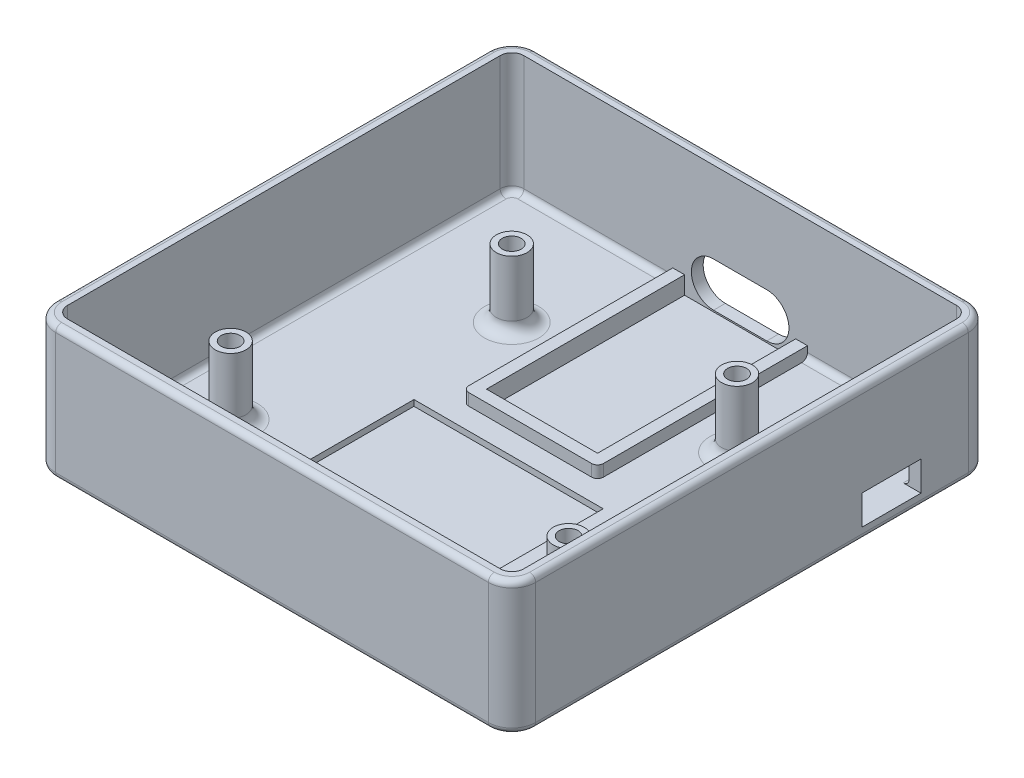
SolidWorks part; units mm, degrees
ref_plane "Front Plane" through (0, 0, 0) normal (0, 0, 1) x (1, 0, 0)
ref_plane "Top Plane" through (0, 0, 0) normal (0, 1, 0) x (1, 0, 0)
ref_plane "Right Plane" through (0, 0, 0) normal (1, 0, 0) x (0, 0, -1)
sketch "Sketch1" plane through (0, 0, 0) normal (0, 1, 0) x (1, 0, 0)
  line L1 (-38.575, -38.575) -> (38.575, -38.575)
  line L2 (-38.575, -38.575) -> (-38.575, 38.575)
  line L3 (-38.575, 38.575) -> (38.575, 38.575)
  line L4 (38.575, -38.575) -> (38.575, 38.575)
  line L5 (-38.575, -38.575) -> (38.575, 38.575) construction
  line L6 (-38.575, 38.575) -> (38.575, -38.575) construction
  point P0 (0, 0)
  dimension "D1" = 77.15
extrude "Boss-Extrude1" add sketch "Sketch1" along normal blind 2
sketch "Sketch2" plane through (0, 0, 0) normal (0, 1, 0) x (1, 0, 0)
  line L20 (38.575, -38.575) -> (38.575, 38.575) construction
  line L21 (38.575, 38.575) -> (-38.575, 38.575) construction
  line L22 (-38.575, 38.575) -> (-38.575, -38.575) construction
  line L23 (-38.575, -38.575) -> (38.575, -38.575) construction
  line L24 (40.575, -40.575) -> (40.575, 40.575)
  line L25 (40.575, 40.575) -> (-40.575, 40.575)
  line L26 (-40.575, 40.575) -> (-40.575, -40.575)
  line L27 (-40.575, -40.575) -> (40.575, -40.575)
  line L28 (40.575, -40.575) -> (40.575, 40.575)
  line L29 (40.575, 40.575) -> (-40.575, 40.575)
  line L30 (-40.575, 40.575) -> (-40.575, -40.575)
  line L31 (-40.575, -40.575) -> (40.575, -40.575)
  line L32 (38.575, -38.575) -> (38.575, 38.575)
  line L33 (38.575, 38.575) -> (-38.575, 38.575)
  line L34 (-38.575, 38.575) -> (-38.575, -38.575)
  line L35 (-38.575, -38.575) -> (38.575, -38.575)
  dimension "D1" = 2
extrude "Boss-Extrude2" add sketch "Sketch2" along normal blind 22.5
sketch "Sketch3" plane through (0, 2, 0) normal (0, 1, 0) x (1, 0, 0)
  line L0 (28.58, -19) -> (-28.58, -19) construction
  line L2 (19.05, 19) -> (-19.05, 19) construction
  circle A2 centre (-28.58, -19) radius 1.6
  circle A3 centre (28.58, -19) radius 1.6
  circle A4 centre (19.05, 19) radius 1.6
  circle A5 centre (-19.05, 19) radius 1.6
  circle A6 centre (-28.58, -19) radius 2.6
  circle A7 centre (-19.05, 19) radius 2.6
  circle A8 centre (28.58, -19) radius 2.6
  circle A9 centre (19.05, 19) radius 2.6
  point P0 (0, 0)
  point P2 (0, 19)
  point P17 (0, -19)
  dimension "D3" = 1
  dimension "D4" = 19
  dimension "D1" = 3.2
  dimension "D2" = 38.1
  dimension "D5" = 57.16
  dimension "D6" = 19
extrude "Boss-Extrude4" add sketch "Sketch3" along normal offset from surface (11.5 mm away) 9 up to face at (0, 22.5, 0)
sketch "Sketch4" plane through (0, 0, 0) normal (1, 0, 0) x (0, 0, -1)
  line L0 (0, 0) -> (0, 22.5) construction
  line L1 (-40.575, 22.5) -> (40.575, 22.5) construction
sketch "Sketch11" plane through (0, 2, 0) normal (0, 1, 0) x (1, 0, 0)
  line L0 (-15, -31.575) -> (-15, -1.575)
  line L6 (-16, -32.575) -> (16, -32.575)
  line L7 (-16, -32.575) -> (-16, -0.575)
  line L8 (-16, -0.575) -> (16, -0.575)
  line L9 (16, -32.575) -> (16, -0.575)
  line L10 (-16, -32.575) -> (16, -0.575) construction
  line L11 (-16, -0.575) -> (16, -32.575) construction
  line L12 (38.575, 38.575) -> (-38.575, 38.575) construction
  line L13 (-8.89, 38.575) -> (8.89, 38.575) construction
  line L14 (-8.89, 38.575) -> (-8.89, 5.575) construction
  line L15 (-8.89, 5.575) -> (8.89, 5.575) construction
  line L16 (8.89, 38.575) -> (8.89, 5.575) construction
  line L17 (-8.89, 38.575) -> (8.89, 5.575) construction
  line L18 (-8.89, 5.575) -> (8.89, 38.575) construction
  line L27 (-15, -1.575) -> (15, -1.575)
  line L28 (15, -31.575) -> (15, -1.575)
  line L29 (-15, -31.575) -> (15, -31.575)
  line L30 (0, -12.1) -> (0, 12.1) construction
  line L31 (4, 38.575) -> (5.5, 38.575)
  line L32 (4, 38.575) -> (4, 10.575)
  line L33 (4, 10.575) -> (5.5, 10.575)
  line L34 (5.5, 38.575) -> (5.5, 10.575)
  line L35 (-4, 10.575) -> (-5.5, 10.575)
  line L36 (-5.5, 38.575) -> (-5.5, 10.575)
  line L37 (-4, 38.575) -> (-5.5, 38.575)
  line L38 (-4, 38.575) -> (-4, 10.575)
  line L39 (-38.575, -38.575) -> (38.575, -38.575) construction
  point P1 (0, 22.075)
  point P6 (0, -16.575)
  dimension "D1" = 33
  dimension "D2" = 17.78
  dimension "D3" = 1
  dimension "D4" = 30
  dimension "D5" = 6
  dimension "D6" = 30
  dimension "D7" = 4
  dimension "D8" = 1.5
  dimension "D9" = 5
extrude "Boss-Extrude7" [suppressed] add sketch "Sketch11" along normal blind 1 contours L35 L36 L37 L38 | L32 L31 L34 L33
sketch "Sketch17" plane through (0, 2, 0) normal (0, 1, 0) x (1, 0, 0)
  line L16 (9.39, 11.075) -> (11.39, 11.075)
  line L17 (11.39, 11.075) -> (11.39, 3.075)
  line L18 (11.39, 3.075) -> (-11.39, 3.075)
  line L19 (-9.39, 5.075) -> (-9.39, 38.575)
  line L20 (9.39, 5.075) -> (-9.39, 5.075)
  line L21 (9.39, 38.575) -> (9.39, 5.075)
  line L22 (-9.39, 5.075) -> (-9.39, 11.075)
  line L23 (9.39, 5.075) -> (-9.39, 5.075)
  line L24 (9.39, 11.075) -> (9.39, 5.075)
  line L25 (-11.39, 3.075) -> (-11.39, 11.075)
  line L26 (-11.39, 11.075) -> (-9.39, 11.075)
  dimension "D1" = 0.5
  dimension "D2" = 2
  dimension "D3" = 2
  dimension "D4" = 8
extrude "Boss-Extrude8" [suppressed] add sketch "Sketch17" along normal blind 2
sketch "Sketch15" plane through (0, 2, 0) normal (0, 1, 0) x (1, 0, 0)
  line L0 (-16, -0.575) -> (-16, -8.575)
  line L1 (-16, -32.575) -> (-16, -0.575) construction
  line L2 (-16, -8.575) -> (-18, -8.575)
  line L3 (-18, -8.575) -> (-18, 1.425)
  line L4 (-18, 1.425) -> (-11, 1.425)
  line L5 (-11, 1.425) -> (-11, -0.575)
  line L6 (-16, -0.575) -> (16, -0.575) construction
  line L7 (-11, -0.575) -> (-16, -0.575)
  line L8 (-18, -24.575) -> (-16, -24.575)
  line L9 (-16, -24.575) -> (-16, -32.575)
  line L10 (-16, -32.575) -> (-11, -32.575)
  line L11 (-16, -32.575) -> (16, -32.575) construction
  line L12 (-11, -32.575) -> (-11, -34.575)
  line L13 (-11, -34.575) -> (-18, -34.575)
  line L14 (-18, -24.575) -> (-18, -34.575)
  line L15 (0, -12.1) -> (0, 12.1) construction
  line L16 (18, -24.575) -> (16, -24.575)
  line L17 (16, -24.575) -> (16, -32.575)
  line L18 (16, -32.575) -> (11, -32.575)
  line L19 (11, -32.575) -> (11, -34.575)
  line L20 (11, -34.575) -> (18, -34.575)
  line L21 (18, -24.575) -> (18, -34.575)
  line L22 (11, 1.425) -> (11, -0.575)
  line L23 (18, 1.425) -> (11, 1.425)
  line L24 (18, -8.575) -> (18, 1.425)
  line L25 (16, -8.575) -> (18, -8.575)
  line L26 (16, -0.575) -> (16, -8.575)
  line L27 (11, -0.575) -> (16, -0.575)
  dimension "D1" = 7
  dimension "D2" = 10
  dimension "D4" = 2
extrude "Boss-Extrude6" [suppressed] add sketch "Sketch15" along normal blind 1.5 contours L7 L0 L2 L3 L4 L5 | L22 L27 L26 L25 L24 L23 | L14 L13 L12 L10 L9 L8 | L16 L17 L18 L19 L20 L21
sketch "Sketch18" plane through (0, 2, 0) normal (0, 1, 0) x (1, 0, 0)
  line L0 (16, -32.575) -> (16, -0.575) construction
  line L1 (-16, -0.575) -> (16, -0.575) construction
  line L2 (-16, -32.575) -> (-16, -0.575) construction
  line L3 (-16, -32.575) -> (16, -32.575) construction
  line L4 (16, -32.575) -> (16, -0.575)
  line L5 (-16, -0.575) -> (16, -0.575)
  line L6 (-16, -32.575) -> (-16, -0.575)
  line L7 (-16, -32.575) -> (16, -32.575)
  line L21 (-8.89, 38.575) -> (8.89, 38.575) construction
  line L22 (-9.39, 38.575) -> (9.39, 38.575)
  line L24 (-9.39, 5.075) -> (-9.39, 38.575)
  line L25 (9.39, 5.075) -> (-9.39, 5.075)
  line L26 (9.39, 38.575) -> (9.39, 5.075)
  line L27 (-9.39, 5.075) -> (-9.39, 38.575)
  line L28 (9.39, 5.075) -> (-9.39, 5.075)
  line L29 (9.39, 38.575) -> (9.39, 5.075)
  dimension "D1" = 0.5
extrude "Cut-Extrude4" cut sketch "Sketch18" against normal offset from surface (1 mm away) 1 up to face at (0, 0, 0)
sketch "Sketch19" plane through (0, 2, 0) normal (0, 1, 0) x (1, 0, 0)
  line L0 (-9.39, 38.575) -> (-9.39, 5.075) construction
  line L1 (-9.39, 5.075) -> (9.39, 5.075) construction
  line L2 (9.39, 5.075) -> (9.39, 38.575) construction
  line L3 (-9.39, 38.575) -> (-9.39, 5.075)
  line L4 (-9.39, 5.075) -> (9.39, 5.075)
  line L5 (9.39, 5.075) -> (9.39, 38.575)
  line L6 (-11.39, 38.575) -> (-11.39, 3.075)
  line L7 (-11.39, 3.075) -> (11.39, 3.075)
  line L8 (11.39, 3.075) -> (11.39, 38.575)
  line L9 (11.39, 38.575) -> (9.39, 38.575)
  line L10 (-9.39, 38.575) -> (-11.39, 38.575)
  dimension "D1" = 2
extrude "Boss-Extrude9" add sketch "Sketch19" along normal blind 2
sketch "Sketch7" plane through (0, 0, 0) normal (0, -1, 0) x (1, 0, 0)
  line L0 (40.575, -40.575) -> (-40.575, -40.575) construction
  line L1 (-40.575, -40.575) -> (-40.575, 40.575) construction
  line L2 (0, 0) -> (-24.575, -24.575) construction
  circle A0 centre (-24.575, -24.575) radius 6.35
  circle A1 centre (-24.575, 24.575) radius 6.35
  circle A2 centre (24.575, 24.575) radius 6.35
  circle A3 centre (24.575, -24.575) radius 6.35
  dimension "D1" = 12.7
  dimension "D4" = 4
extrude "Cut-Extrude1" cut sketch "Sketch7" against normal offset from surface (1 mm away) 1 up to face at (0, 2, 16.575)
sketch "Sketch10" plane through (0, 0, -38.575) normal (0, 0, -1) x (-1, 0, 0)
  line L0 (-4.5, 5) -> (4.5, 5) construction
  line L1 (-4.5, 8.75) -> (4.5, 8.75)
  line L2 (-4.5, 1.25) -> (4.5, 1.25)
  line L3 (-38.575, 2) -> (-11.39, 2) construction
  line L4 (-38.575, 2) -> (-11.39, 2) construction
  line L5 (-9.39, 1) -> (9.39, 1) construction
  arc A1 (-4.5, 8.75) -> (-4.5, 1.25) centre (-4.5, 5) ccw
  arc A2 (4.5, 1.25) -> (4.5, 8.75) centre (4.5, 5) ccw
  point P2 (0, 5)
  dimension "D1" = 9
  dimension "D2" = 7.5
  dimension "D3" = 4
extrude "Cut-Extrude2" cut sketch "Sketch10" along normal up to surface (2 mm away) up to face at (0, 11.25, -40.575)
sketch "Sketch16" plane through (38.575, 0, 0) normal (-1, 0, 0) x (0, 0, 1)
  line L0 (38.575, 2) -> (-38.575, 2) construction
  line L1 (-28.575, 2) -> (-18.575, 2)
  line L2 (-28.575, 2) -> (-28.575, 7)
  line L3 (-28.575, 7) -> (-18.575, 7)
  line L4 (-18.575, 2) -> (-18.575, 7)
  dimension "D1" = 10
  dimension "D2" = 5
  dimension "D3" = 10
extrude "Cut-Extrude3" cut sketch "Sketch16" against normal up to surface (2 mm away) up to face at (40.575, 11.25, 0)
fillet "Fillet1" radius 2 4 edges at (28.58, 2, 16.4) (19.05, 2, -21.6) (-28.58, 2, 16.4) (-19.05, 2, -21.6)
fillet "Fillet2" [suppressed] radius 1
chamfer "Chamfer1" [suppressed] distance 2.5 angle 45
fillet "Fillet3" [suppressed] radius 2 tangent propagation no
fillet "Fillet6" radius 4 4 edges at (40.575, 11.25, -40.575) (-40.575, 11.25, -40.575) (-40.575, 11.25, 40.575) (40.575, 11.25, 40.575)
fillet "Fillet7" radius 2 4 edges at (38.575, 12.25, -38.575) (-38.575, 12.25, -38.575) (-38.575, 12.25, 38.575) (38.575, 12.25, 38.575)
fillet "Fillet5" radius 1 16 edges at (0, 22.5, 40.575) (-40.575, 22.5, 0) (0, 22.5, -40.575) (0, 0, 40.575) (-40.575, 0, 0) (0, 0, -40.575) (40.575, 22.5, 0) (40.575, 0, 0) (39.4034, 0, 39.4034) (-39.4034, 0, 39.4034) (-39.4034, 0, -39.4034) (39.4034, 0, -39.4034) (39.4034, 22.5, 39.4034) (-39.4034, 22.5, 39.4034) (-39.4034, 22.5, -39.4034) (39.4034, 22.5, -39.4034)
fillet "Fillet9" radius 1 10 edges at (23.9825, 2, -38.575) (37.9892, 2, -37.9892) (38.575, 2, 9) (37.9892, 2, 37.9892) (0, 2, 38.575) (-37.9892, 2, 37.9892) (-38.575, 2, 0) (-37.9892, 2, -37.9892) (38.575, 2, -32.575) (-23.9825, 2, -38.575)
fillet "Fillet10" radius 1 2 edges at (-11.39, 3, -3.075) (11.39, 3, -3.075)
